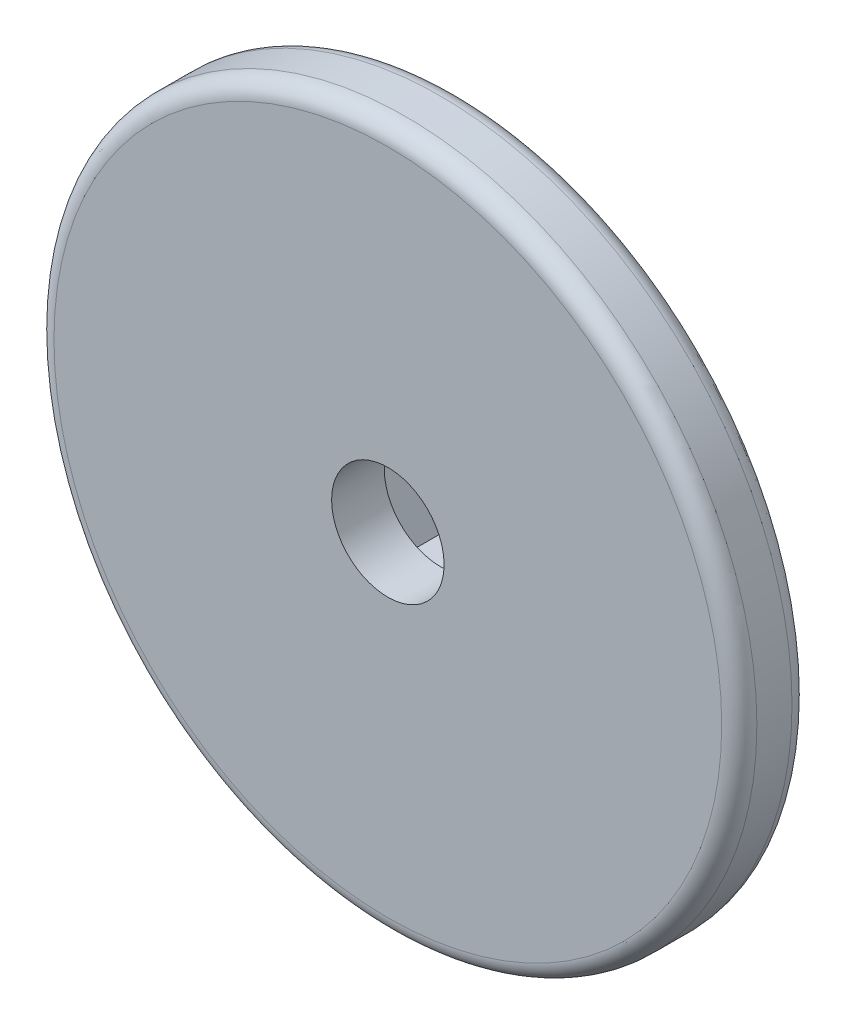
SolidWorks part; units mm, degrees
material "ABS"
ref_plane "Front Plane" through (0, 0, 0) normal (0, 0, 1) x (1, 0, 0)
ref_plane "Top Plane" through (0, 0, 0) normal (0, 1, 0) x (1, 0, 0)
ref_plane "Right Plane" through (0, 0, 0) normal (1, 0, 0) x (0, 0, -1)
sketch "Sketch1" plane through (0, 0, 0) normal (0, 1, 0) x (1, 0, 0)
  line L0 (0, 0) -> (9.5, 0)
  line L1 (10, 0.5) -> (10, 1.5)
  line L2 (9.5, 2) -> (7, 2)
  line L3 (7, 2) -> (6.193, 4)
  line L4 (6.193, 4) -> (4.693, 4)
  line L5 (4.693, 4) -> (4.0351, 3.5)
  line L6 (4.0351, 3.5) -> (0, 3.5)
  line L7 (0, 3.5) -> (0, 0)
  arc A0 (9.5, 0) -> (10, 0.5) centre (9.5, 0.5) ccw
  arc A1 (10, 1.5) -> (9.5, 2) centre (9.5, 1.5) ccw
  point P11 (10, 0)
  point P14 (10, 2)
  dimension "D7" = 0.5
  dimension "D1" = 10
  dimension "D2" = 2
  dimension "D3" = 4
  dimension "D4" = 3.5
  dimension "D5" = 1.5
  dimension "D6" = 3
revolve "Revolve1" add sketch "Sketch1" angle 360 about L7
sketch "Sketch2" plane through (0, 0, -3.5) normal (0, 0, -1) x (-1, 0, 0)
  circle A0 centre (0, 0) radius 1.6
  dimension "D1" = 3.2
extrude "Cut-Extrude1" cut sketch "Sketch2" against normal through all
sketch "Sketch3" plane through (0, 0, -3.5) normal (0, 0, -1) x (-1, 0, 0)
  line L1 (-1.2934, -2.6773) -> (1.6719, -2.4588)
  line L2 (1.6719, -2.4588) -> (2.9653, 0.2186)
  line L3 (2.9653, 0.2186) -> (1.2934, 2.6773)
  line L4 (1.2934, 2.6773) -> (-1.6719, 2.4588)
  line L5 (-1.6719, 2.4588) -> (-2.9653, -0.2186)
  line L6 (-2.9653, -0.2186) -> (-1.2934, -2.6773)
  circle A0 centre (0, 0) radius 2.575 construction
  dimension "D1" = 5.15
extrude "Cut-Extrude2" cut sketch "Sketch3" against normal blind 2
